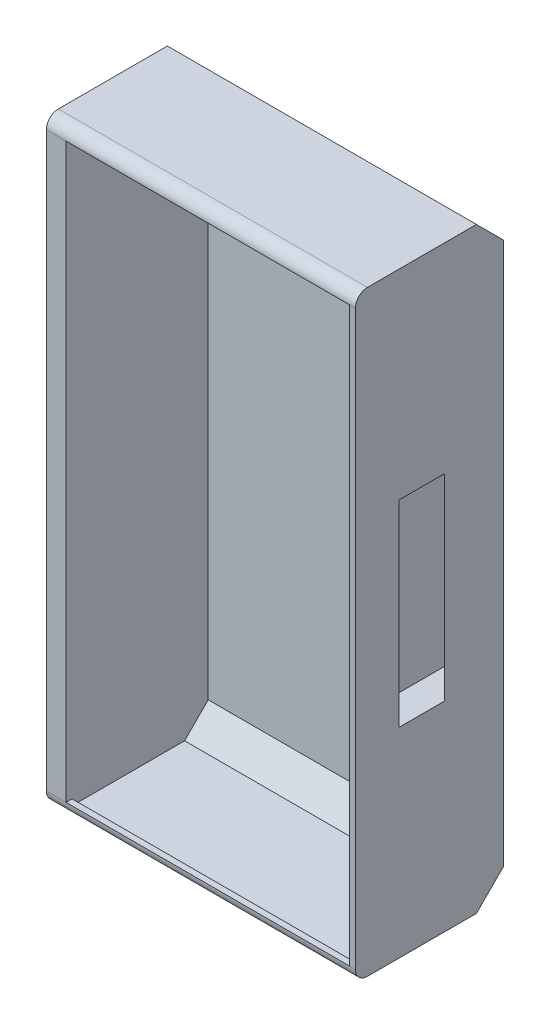
SolidWorks part; units mm, degrees
ref_plane "Front Plane" through (0, 0, 0) normal (1, 0, 0) x (0, 1, 0)
ref_plane "Top Plane" through (0, 0, 0) normal (0, 0, 1) x (0, 1, 0)
ref_plane "Right Plane" through (0, 0, 0) normal (0, 1, 0) x (-1, 0, 0)
sketch "Sketch1" plane through (0, 0, 0) normal (1, 0, 0) x (0, 1, 0)
  line L12 (-98.46, -42.4834) -> (-89.4834, -51.46)
  line L13 (-89.4834, -51.46) -> (89.4834, -51.46)
  line L14 (89.4834, -51.46) -> (98.46, -42.4834)
  line L15 (98.46, -42.4834) -> (98.46, -6.5)
  line L16 (94.5, -2.54) -> (-94.5, -2.54)
  line L17 (-98.46, -6.5) -> (-98.46, -42.4834)
  line L18 (-98.46, -42.4834) -> (-89.4834, -51.46)
  line L19 (-89.4834, -51.46) -> (89.4834, -51.46)
  line L20 (89.4834, -51.46) -> (98.46, -42.4834)
  line L21 (98.46, -42.4834) -> (98.46, -6.5)
  line L22 (94.5, -2.54) -> (-94.5, -2.54)
  line L23 (-98.46, -6.5) -> (-98.46, -42.4834)
  arc A4 (98.46, -6.5) -> (94.5, -2.54) centre (94.5, -6.5) ccw
  arc A5 (-94.5, -2.54) -> (-98.46, -6.5) centre (-94.5, -6.5) ccw
  arc A6 (98.46, -6.5) -> (94.5, -2.54) centre (94.5, -6.5) ccw
  arc A7 (-94.5, -2.54) -> (-98.46, -6.5) centre (-94.5, -6.5) ccw
  dimension "D1" = 0.04
extrude "Boss-Extrude1" add sketch "Sketch1" along normal up to surface (102 mm away) contours L18 L19 L20 L21 A6 L22 A7 L23
ref_plane "Plane3" through (0, 0, 0) normal (0, 1, 0) x (1, 0, 0)
sketch "Sketch11" plane through (0, 0, 0) normal (0, 1, 0) x (1, 0, 0)
  line L0 (102, 24.4917) -> (104.8284, 21.6633)
  line L1 (102, 6.5) -> (102, 42.4834) construction
  line L2 (102, 24.4917) -> (92.1005, 34.3912)
  dimension "D1" = 14
  dimension "D2" = 4
  dimension "D3" = 45
sketch "Sketch12" plane through (102, 0, 0) normal (1, 0, 0) x (0, 1, 0)
  line L0 (0, -24.4917) -> (0, -21.6633) construction
  line L1 (-32.5, -31.9917) -> (32.5, -31.9917)
  line L2 (-32.5, -31.9917) -> (-32.5, -16.9917)
  line L3 (-32.5, -16.9917) -> (32.5, -16.9917)
  line L4 (32.5, -31.9917) -> (32.5, -16.9917)
  line L5 (-32.5, -31.9917) -> (32.5, -16.9917) construction
  line L6 (-32.5, -16.9917) -> (32.5, -31.9917) construction
  line L7 (0, -24.4917) -> (0, -34.3912) construction
  line L10 (89.4834, -51.46) -> (-89.4834, -51.46) construction
  point P0 (0, -24.4917)
  dimension "D1" = 65
  dimension "D2" = 15
  dimension "D3" = 26.9683
sweep "Cut-Sweep1" cut profiles "Sketch12" path "Sketch11"
shell "Shell1" thickness 2 removed face at (51, 0, -2.54)
sketch "Sketch8" plane through (2, 0, 0) normal (1, 0, 0) x (0, 1, 0)
  line L11 (-10, -27) -> (-10, -17)
  line L12 (-10, -17) -> (10, -17)
  line L13 (10, -27) -> (10, -17)
  line L15 (-98.46, -42.4834) -> (-89.4834, -51.46)
  line L16 (-89.4834, -51.46) -> (89.4834, -51.46)
  line L17 (89.4834, -51.46) -> (98.46, -42.4834)
  line L18 (98.46, -42.4834) -> (98.46, -6.5)
  line L19 (94.5, -2.54) -> (-94.5, -2.54)
  line L20 (-98.46, -6.5) -> (-98.46, -42.4834)
  line L21 (-98.46, -42.4834) -> (-89.4834, -51.46)
  line L22 (-89.4834, -51.46) -> (89.4834, -51.46)
  line L23 (89.4834, -51.46) -> (98.46, -42.4834)
  line L24 (98.46, -42.4834) -> (98.46, -6.5)
  line L25 (94.5, -2.54) -> (-94.5, -2.54)
  line L26 (-98.46, -6.5) -> (-98.46, -42.4834)
  arc A0 (-10, -27) -> (10, -27) centre (0, -27) ccw
  arc A5 (98.46, -6.5) -> (94.5, -2.54) centre (94.5, -6.5) ccw
  arc A6 (-94.5, -2.54) -> (-98.46, -6.5) centre (-94.5, -6.5) ccw
  arc A7 (98.46, -6.5) -> (94.5, -2.54) centre (94.5, -6.5) ccw
  arc A8 (-94.5, -2.54) -> (-98.46, -6.5) centre (-94.5, -6.5) ccw
  point P4 (0, -51.46)
  dimension "D2" = 20
  dimension "D3" = 24.46
  dimension "D4" = 10
  dimension "D5" = 20
  dimension "D1" = 0
extrude "Boss-Extrude2" add sketch "Sketch8" along normal blind 2.5
sketch "Sketch10" plane through (4.5, 0, 0) normal (1, 0, 0) x (0, 1, 0)
  line L8 (94.5, -4.54) -> (94.5, -2.54)
  line L9 (94.5, -2.54) -> (-94.5, -2.54)
  line L10 (-94.5, -2.54) -> (-94.5, -4.54)
  line L11 (-96.46, -6.5) -> (-96.46, -41.655)
  line L12 (-96.46, -41.655) -> (-88.655, -49.46)
  line L13 (-88.655, -49.46) -> (88.655, -49.46)
  line L14 (88.655, -49.46) -> (96.46, -41.655)
  line L15 (96.46, -41.655) -> (96.46, -6.5)
  line L16 (94.5, -4.54) -> (94.5, -2.54)
  line L17 (94.5, -2.54) -> (-94.5, -2.54)
  line L18 (-94.5, -2.54) -> (-94.5, -4.54)
  line L19 (-96.46, -6.5) -> (-96.46, -41.655)
  line L20 (-96.46, -41.655) -> (-88.655, -49.46)
  line L21 (-88.655, -49.46) -> (88.655, -49.46)
  line L22 (88.655, -49.46) -> (96.46, -41.655)
  line L23 (96.46, -41.655) -> (96.46, -6.5)
  arc A2 (-94.5, -4.54) -> (-96.46, -6.5) centre (-94.5, -6.5) ccw
  arc A3 (96.46, -6.5) -> (94.5, -4.54) centre (94.5, -6.5) ccw
  arc A4 (-94.5, -4.54) -> (-96.46, -6.5) centre (-94.5, -6.5) ccw
  arc A5 (96.46, -6.5) -> (94.5, -4.54) centre (94.5, -6.5) ccw
  dimension "D1" = 0
extrude "Boss-Extrude3" add sketch "Sketch10" along normal blind 2
chamfer "Chamfer1" distance 20 angle 45 1 edges at (100, 0, -36.8201) first distance on face at (100, 0, -20.8578)
